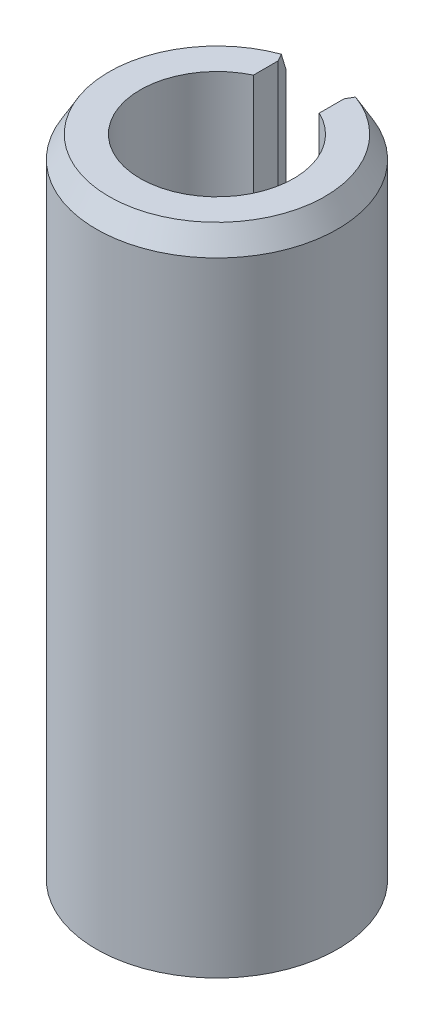
SolidWorks part; units mm, degrees
ref_plane "Plano frontal" through (0, 0, 0) normal (0, 0, 1) x (1, 0, 0)
ref_plane "Plano superior" through (0, 0, 0) normal (0, 1, 0) x (1, 0, 0)
ref_plane "Plano direito" through (0, 0, 0) normal (1, 0, 0) x (0, 0, -1)
sketch "Esboço1" plane through (0, 0, 0) normal (0, 1, 0) x (1, 0, 0)
  circle A0 centre (0, 0) radius 2.75
  circle A1 centre (0, 0) radius 1.75
  dimension "D1" = 5.5
  dimension "D2" = 3.5
extrude "Ressalto-extrusão1" add sketch "Esboço1" along normal blind 15
sketch "Esboço2" plane through (0, 15, 0) normal (0, 1, 0) x (1, 0, 0)
  line L0 (0, 0) -> (0, 3.1315) construction
  line L2 (-0.75, 3.1315) -> (0.75, 3.1315)
  line L3 (-0.75, 3.1315) -> (-0.75, 0.3636)
  line L4 (-0.75, 0.3636) -> (0.75, 0.3636)
  line L5 (0.75, 3.1315) -> (0.75, 0.3636)
  dimension "D1" = 1.5
extrude "Corte-extrusão1" cut sketch "Esboço2" against normal through all
chamfer "Chanfro1" distance 0.5 angle 30 2 edges at (0.75, 7.5, -2.6458) (-0.75, 7.5, -2.6458) first distance on face at (0.75, 7.5, -2.1134) first distance on face at (-0.75, 7.5, -2.1134)
chamfer "Chanfro2" distance 0.5 angle 30 2 edges at (0, 0, 2.75) (0, 15, 2.75) first distance on face at (0, 0, -0.6562) first distance on face at (0, 7.5, 0.0926)
